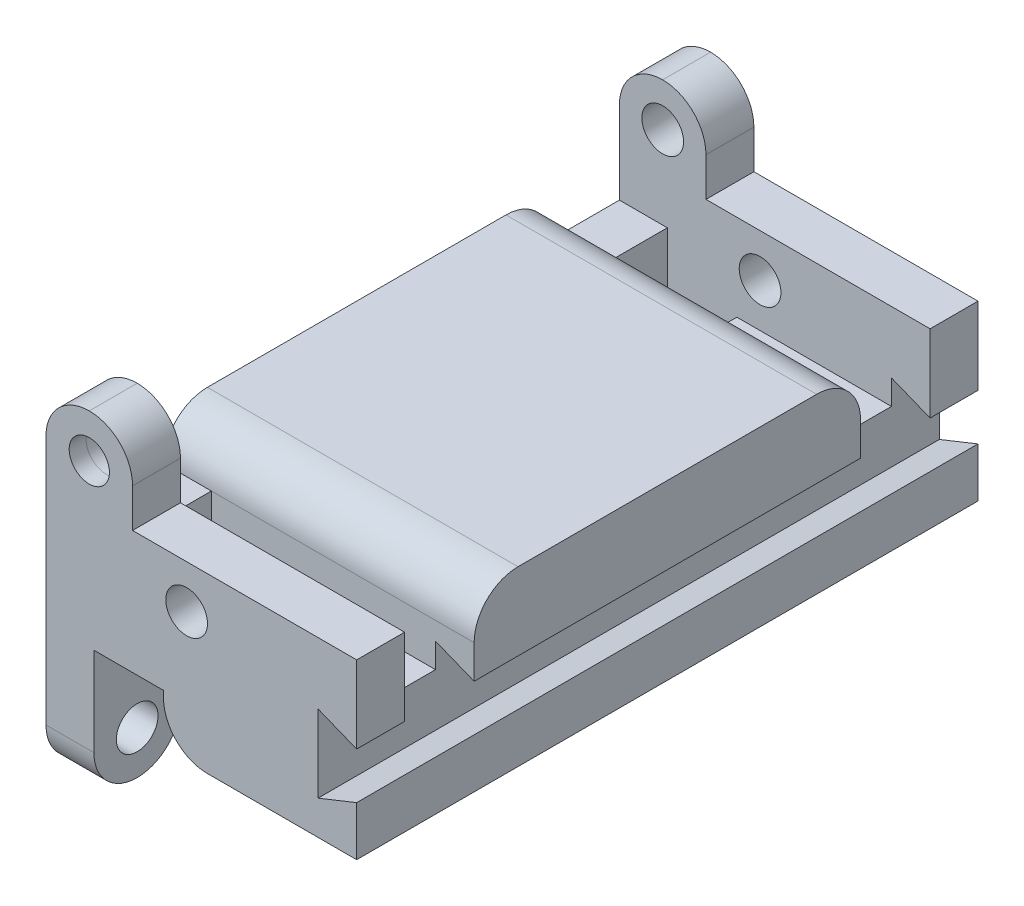
SolidWorks part; units mm, degrees
ref_plane "Plano frontal" through (0, 0, 0) normal (0, 0, 1) x (1, 0, 0)
ref_plane "Plano superior" through (0, 0, 0) normal (0, 1, 0) x (1, 0, 0)
ref_plane "Plano direito" through (0, 0, 0) normal (1, 0, 0) x (0, 0, -1)
sketch "Esboço1" plane through (0, 0, 0) normal (0, 0, 1) x (1, 0, 0)
  line L0 (0, 0) -> (5.6, 0)
  line L1 (0, 0) -> (0, -11.45)
  line L2 (0, -11.45) -> (40.2, -11.45)
  line L3 (40.2, -11.45) -> (40.2, 0)
  line L4 (40.2, 0) -> (34.6, 0)
  line L5 (5.6, 0) -> (5.6, -5.85)
  line L6 (5.6, -5.85) -> (34.6, -5.85)
  line L7 (34.6, -5.85) -> (34.6, 0)
  circle A0 centre (2.8, -3.35) radius 1.35
  circle A1 centre (37.4, -3.35) radius 1.35
  circle A3 centre (31.1, -8.65) radius 1.35
  circle A4 centre (9.1, -8.65) radius 1.35
  dimension "D6" = 2.7
  dimension "D7" = 3.35
  dimension "D8" = 2.7
  dimension "D9" = 2.8
  dimension "D10" = 2.8
  dimension "D11" = 2.7
  dimension "D12" = 2.7
  dimension "D13" = 3.5
  dimension "D14" = 3.5
  dimension "D15" = 2.8
  dimension "D16" = 2.8
  dimension "D17" = 3.35
  dimension "D1" = 5.6
  dimension "D2" = 11.45
  dimension "D3" = 40.2
  dimension "D4" = 5.6
  dimension "D5" = 5.85
extrude "Ressalto-extrusão1" add sketch "Esboço1" along normal blind 2
sketch "Esboço3" plane through (0, -11.45, 0) normal (0, -1, 0) x (1, 0, 0)
  line L1 (0, 0) -> (40.2, 0)
  line L2 (0, 0) -> (0, 2)
  line L3 (0, 2) -> (40.2, 2)
  line L4 (40.2, 0) -> (40.2, 2)
extrude "Ressalto-extrusão2" add sketch "Esboço3" along normal blind 10.08
sketch "Esboço4" plane through (0, 0, 0) normal (0, 0, -1) x (-1, 0, 0)
  line L0 (0, 0) -> (0, -21.53) construction
  line L1 (-40.2, -21.53) -> (-37.1, -21.53)
  line L2 (-40.2, -21.53) -> (-40.2, -8.69)
  line L3 (-40.2, -8.69) -> (-37.1, -8.69)
  line L4 (-37.1, -21.53) -> (-37.1, -8.69)
  line L5 (0, -8.69) -> (-3.1, -8.69)
  line L6 (0, -8.69) -> (0, -21.53)
  line L7 (0, -21.53) -> (-3.1, -21.53)
  line L8 (-3.1, -8.69) -> (-3.1, -21.53)
  line L9 (0, -21.53) -> (-40.2, -21.53) construction
  dimension "D1" = 12.84
  dimension "D2" = 3.1
  dimension "D3" = 3.1
  dimension "D4" = 12.84
extrude "Ressalto-extrusão3" add sketch "Esboço4" along normal blind 34
sketch "Esboço5" plane through (37.1, 0, 0) normal (-1, 0, 0) x (0, 0, 1)
  line L0 (0, -21.53) -> (0, -8.69) construction
  line L2 (-34, -21.53) -> (0, -21.53) construction
  line L4 (-34, -21.53) -> (-34, -8.69) construction
  circle A0 centre (-6, -14.25) radius 1.35
  circle A2 centre (-28, -14.25) radius 1.35
  dimension "D1" = 2.7
  dimension "D2" = 2.7
  dimension "D3" = 6
  dimension "D4" = 7.28
  dimension "D5" = 7.28
  dimension "D6" = 6
extrude "Corte-extrusão1" cut sketch "Esboço5" against normal through all both and the other way through all
sketch "Esboço7" plane through (0, 0, 0) normal (0, 0, -1) x (-1, 0, 0)
  line L0 (0, 0) -> (0, -8.69) construction
  line L1 (-37.1, -21.53) -> (0, -21.53)
  line L2 (-37.1, -21.53) -> (-37.1, -18.29)
  line L3 (-37.1, -18.29) -> (0, -18.29)
  line L4 (0, -21.53) -> (0, -18.29)
  dimension "D1" = 3.24
extrude "Corte-extrusão2" cut sketch "Esboço7" against normal blind 2
sketch "Esboço12" plane through (0, 0, -34) normal (0, 0, -1) x (-1, 0, 0)
  line L0 (-5.6, 0) -> (0, 0)
  line L1 (-40.2, 0) -> (-34.6, 0)
  line L2 (-40.2, 0) -> (-40.2, -18.29)
  line L3 (-40.2, -18.29) -> (0, -18.29)
  line L4 (0, 0) -> (0, -18.29)
  line L6 (-34.6, 0) -> (-34.6, -5.85)
  line L7 (-34.6, -5.85) -> (-5.6, -5.85)
  line L8 (-5.6, 0) -> (-5.6, -5.85)
  circle A1 centre (-31.1, -8.65) radius 1.35
  circle A2 centre (-9.1, -8.65) radius 1.35
  circle A3 centre (-2.8, -3.35) radius 1.35
  circle A4 centre (-37.4, -3.35) radius 1.35
extrude "Ressalto-extrusão5" add sketch "Esboço12" along normal blind 2
sketch "Esboço18" plane through (0, 0, 0) normal (0, 0, 1) x (1, 0, 0)
  line L0 (3.1, -18.29) -> (3.1, -21.53) construction
  line L1 (0, -18.29) -> (3.1, -18.29)
  line L2 (0, -18.29) -> (0, -21.53)
  line L3 (0, -21.53) -> (3.1, -21.53)
  line L4 (3.1, -18.29) -> (3.1, -21.53)
extrude "Ressalto-extrusão6" add sketch "Esboço18" along normal blind 2
sketch "Esboço19" plane through (0, 0, -34) normal (0, 0, -1) x (-1, 0, 0)
  line L0 (0, -21.53) -> (0, -18.29) construction
  line L1 (-3.1, -21.53) -> (0, -21.53)
  line L2 (-3.1, -21.53) -> (-3.1, -18.29)
  line L3 (-3.1, -18.29) -> (0, -18.29)
  line L4 (0, -21.53) -> (0, -18.29)
  line L6 (-40.2, -21.53) -> (-37.1, -21.53)
  line L7 (-40.2, -21.53) -> (-40.2, -18.29)
  line L8 (-40.2, -18.29) -> (-37.1, -18.29)
  line L9 (-37.1, -21.53) -> (-37.1, -18.29)
extrude "Ressalto-extrusão7" add sketch "Esboço19" along normal blind 2
sketch "Esboço21" plane through (0, 0, 2) normal (0, 0, 1) x (1, 0, 0)
  line L0 (37.1, -21.53) -> (40.2, -21.53)
  line L1 (0, 0) -> (5.6, 0)
  line L2 (0, 0) -> (0, -21.53)
  line L3 (0, -21.53) -> (3.1, -21.53)
  line L4 (40.2, 0) -> (40.2, -21.53)
  line L6 (5.6, 0) -> (5.6, -5.85)
  line L7 (5.6, -5.85) -> (34.6, -5.85)
  line L8 (34.6, 0) -> (34.6, -5.85)
  line L9 (3.1, -18.29) -> (37.1, -18.29)
  line L10 (3.1, -18.29) -> (3.1, -21.53)
  line L12 (37.1, -18.29) -> (37.1, -21.53)
  line L13 (34.6, 0) -> (40.2, 0)
  circle A0 centre (2.8, -3.35) radius 1.3018
  circle A1 centre (9.1, -8.65) radius 1.35
  circle A2 centre (31.1, -8.65) radius 1.35
  circle A3 centre (37.4, -3.35) radius 1.35
extrude "Ressalto-extrusão8" add sketch "Esboço21" along normal blind 1.1
sketch "Esboço22" plane through (0, 0, -36) normal (0, 0, -1) x (-1, 0, 0)
  line L0 (-5.6, 0) -> (0, 0)
  line L1 (-40.2, 0) -> (-34.6, 0)
  line L2 (-40.2, 0) -> (-40.2, -21.53)
  line L3 (-40.2, -21.53) -> (-37.1, -21.53)
  line L4 (0, 0) -> (0, -21.53)
  line L6 (-37.1, -21.53) -> (-37.1, -18.29)
  line L7 (-37.1, -18.29) -> (-3.1, -18.29)
  line L8 (-3.1, -21.53) -> (-3.1, -18.29)
  line L9 (-34.6, -5.85) -> (-5.6, -5.85)
  line L10 (-34.6, -5.85) -> (-34.6, 0)
  line L12 (-5.6, -5.85) -> (-5.6, 0)
  line L13 (-3.1, -21.53) -> (0, -21.53)
  circle A0 centre (-37.4, -3.35) radius 1.35
  circle A1 centre (-31.1, -8.65) radius 1.35
  circle A2 centre (-9.1, -8.65) radius 1.35
  circle A3 centre (-2.8, -3.35) radius 1.35
extrude "Ressalto-extrusão9" add sketch "Esboço22" along normal blind 1.1
sketch "Esboço23" plane through (0, -21.53, 0) normal (0, -1, 0) x (1, 0, 0)
  line L0 (3.1, -37.1) -> (3.1, 3.1) construction
  line L1 (0, 3.1) -> (3.1, 3.1)
  line L2 (0, 3.1) -> (0, -2.5)
  line L3 (0, -2.5) -> (3.1, -2.5)
  line L4 (3.1, 3.1) -> (3.1, -2.5)
  line L5 (40.2, -37.1) -> (40.2, 3.1) construction
  line L6 (0, -37.1) -> (3.1, -37.1)
  line L7 (0, -37.1) -> (0, -31.5)
  line L8 (0, -31.5) -> (3.1, -31.5)
  line L9 (3.1, -37.1) -> (3.1, -31.5)
  line L10 (37.1, -37.1) -> (40.2, -37.1)
  line L11 (37.1, -37.1) -> (37.1, -31.5)
  line L12 (37.1, -31.5) -> (40.2, -31.5)
  line L13 (40.2, -37.1) -> (40.2, -31.5)
  line L15 (37.1, 3.1) -> (40.2, 3.1)
  line L16 (37.1, 3.1) -> (37.1, -2.5)
  line L17 (37.1, -2.5) -> (40.2, -2.5)
  line L18 (40.2, 3.1) -> (40.2, -2.5)
  dimension "D1" = 5.6
  dimension "D2" = 5.6
  dimension "D3" = 5.6
  dimension "D4" = 5.6
extrude "Ressalto-extrusão10" add sketch "Esboço23" along normal blind 5.85
sketch "Esboço24" plane through (0, 0, 0) normal (-1, 0, 0) x (0, 0, 1)
  line L1 (-31.5, -27.38) -> (-31.5, -21.53) construction
  line L2 (3.1, 0) -> (3.1, -27.38) construction
  line L3 (3.1, -27.38) -> (-2.5, -27.38) construction
  line L4 (-31.5, -27.38) -> (-37.1, -27.38) construction
  circle A0 centre (-34.3, -19.55) radius 1.35
  circle A1 centre (0.3, -19.55) radius 1.35
  point P10 (0.3, -27.38)
  dimension "D1" = 2.7
  dimension "D2" = 2.7
  dimension "D3" = 2.8
  dimension "D4" = 2.8
  dimension "D5" = 7.83
  dimension "D6" = 7.83
extrude "Corte-extrusão3" cut sketch "Esboço24" against normal up to surface (40.2 mm away) up to face at (40.2, -14.25, -4.65)
sketch "Esboço25" plane through (0, -18.29, 0) normal (0, -1, 0) x (1, 0, 0)
  line L6 (3.1, -37.1) -> (7.6, -37.1)
  line L7 (3.1, -37.1) -> (3.1, -34)
  line L8 (3.1, -34) -> (7.6, -34)
  line L9 (37.1, -37.1) -> (37.1, -34)
  line L10 (32.6, 3.1) -> (37.1, 3.1)
  line L11 (3.1, 3.1) -> (7.6, 3.1)
  line L16 (3.1, 3.1) -> (3.1, 0)
  line L17 (3.1, 0) -> (7.6, 0)
  line L18 (37.1, 3.1) -> (37.1, 0)
  line L22 (7.6, 3.1) -> (7.6, 0)
  line L25 (37.1, 0) -> (32.6, 0)
  line L26 (32.6, 3.1) -> (32.6, 0)
  line L28 (32.6, -34) -> (37.1, -34)
  line L32 (7.6, -34) -> (7.6, -37.1)
  line L33 (37.1, -37.1) -> (32.6, -37.1)
  line L36 (32.6, -37.1) -> (32.6, -34)
  dimension "D1" = 4.5
  dimension "D2" = 4.5
  dimension "D3" = 4.5
  dimension "D4" = 4.5
sketch "Esboço27" plane through (0, -21.53, 0) normal (0, -1, 0) x (1, 0, 0)
  line L28 (0, -2.5) -> (3.1, -2.5)
  line L29 (0, -2.5) -> (0, -31.5)
  line L30 (0, -31.5) -> (3.1, -31.5)
  line L31 (3.1, -2.5) -> (3.1, -31.5)
  line L32 (40.2, -2.5) -> (37.1, -2.5)
  line L33 (40.2, -2.5) -> (40.2, -31.5)
  line L34 (40.2, -31.5) -> (37.1, -31.5)
  line L35 (37.1, -2.5) -> (37.1, -31.5)
extrude "Corte-extrusão6" cut sketch "Esboço25" against normal blind 4.48
extrude "Corte-extrusão7" cut sketch "Esboço27" against normal blind 4.48
sketch "Esboço28" plane through (0, -18.29, 0) normal (0, -1, 0) x (1, 0, 0)
  line L1 (7.6, 3.1) -> (32.6, 3.1)
  line L2 (7.6, 3.1) -> (7.6, -37.1)
  line L3 (7.6, -37.1) -> (32.6, -37.1)
  line L4 (32.6, 3.1) -> (32.6, -37.1)
extrude "Corte-extrusão8" cut sketch "Esboço28" against normal blind 1.24
sketch "Esboço29" plane through (0, 0, -34) normal (0, 0, 1) x (1, 0, 0)
  line L1 (7.6, -17.05) -> (32.6, -17.05)
  line L2 (7.6, -17.05) -> (7.6, -11.45)
  line L3 (7.6, -11.45) -> (32.6, -11.45)
  line L4 (32.6, -17.05) -> (32.6, -11.45)
  dimension "D1" = 25
  dimension "D2" = 5.6
extrude "Ressalto-extrusão11" add sketch "Esboço29" along normal up to surface (34 mm away) up to face at (32.45, -8.65, 0)
sketch "Esboço31" plane through (0, -8.69, 0) normal (0, 1, 0) x (1, 0, 0)
  line L40 (0, 34) -> (0, 0) construction
  line L49 (0, 29.5) -> (3.1, 29.5)
  line L50 (0, 29.5) -> (0, 4.5)
  line L51 (0, 4.5) -> (3.1, 4.5)
  line L52 (3.1, 29.5) -> (3.1, 4.5)
  line L53 (3.1, 34) -> (3.1, 0) construction
  line L54 (37.1, 34) -> (37.1, 0) construction
  line L55 (37.1, 29.5) -> (40.2, 29.5)
  line L56 (37.1, 29.5) -> (37.1, 4.5)
  line L57 (37.1, 4.5) -> (40.2, 4.5)
  line L58 (40.2, 29.5) -> (40.2, 4.5)
  line L59 (40.2, 34) -> (40.2, 0) construction
  line L60 (0, 34) -> (3.1, 34) construction
  line L62 (40.2, 0) -> (34.6, 0) construction
  line L63 (34.6, 34) -> (40.2, 34) construction
  dimension "D1" = 25
  dimension "D2" = 4.5
  dimension "D3" = 4.5
  dimension "D4" = 4.5
extrude "Ressalto-extrusão12" add sketch "Esboço31" along normal blind 2.84
sketch "Esboço32" plane through (37.1, 0, 0) normal (-1, 0, 0) x (0, 0, 1)
  line L1 (-29.5, -5.85) -> (-4.5, -5.85)
  line L2 (-29.5, -5.85) -> (-29.5, -11.45)
  line L3 (-29.5, -11.45) -> (-4.5, -11.45)
  line L4 (-4.5, -5.85) -> (-4.5, -11.45)
  dimension "D1" = 25
  dimension "D2" = 5.6
extrude "Ressalto-extrusão13" add sketch "Esboço32" along normal up to surface (34 mm away) up to face at (3.1, -15.3325, -17)
fillet "Filete1" radius 2.84 4 edges at (32.6, -17.05, -17) (7.6, -17.05, -17) (20.1, -5.85, -29.5) (20.1, -5.85, -4.5)
sketch "Esboço33" plane through (0, 0, 0) normal (0, 1, 0) x (1, 0, 0)
  line L1 (0, 37.1) -> (5.6, 37.1)
  line L2 (0, 37.1) -> (0, 34)
  line L3 (0, 34) -> (5.6, 34)
  line L4 (5.6, 37.1) -> (5.6, 34)
  line L5 (34.6, 34) -> (40.2, 34)
  line L6 (34.6, 34) -> (34.6, 37.1)
  line L7 (34.6, 37.1) -> (40.2, 37.1)
  line L8 (40.2, 34) -> (40.2, 37.1)
  line L9 (40.2, -3.1) -> (34.6, -3.1)
  line L10 (40.2, -3.1) -> (40.2, 0)
  line L11 (40.2, 0) -> (34.6, 0)
  line L12 (34.6, -3.1) -> (34.6, 0)
  line L13 (5.6, -3.1) -> (0, -3.1)
  line L14 (5.6, -3.1) -> (5.6, 0)
  line L15 (5.6, 0) -> (0, 0)
  line L16 (0, -3.1) -> (0, 0)
extrude "Corte-extrusão9" cut sketch "Esboço33" against normal blind 0.55
sketch "Esboço35" plane through (0, -27.38, 0) normal (0, -1, 0) x (1, 0, 0)
  line L1 (0, -2.5) -> (3.1, -2.5)
  line L2 (0, -2.5) -> (0, 3.1)
  line L3 (0, 3.1) -> (3.1, 3.1)
  line L4 (3.1, -2.5) -> (3.1, 3.1)
  line L5 (37.1, -2.5) -> (40.2, -2.5)
  line L6 (37.1, -2.5) -> (37.1, 3.1)
  line L7 (37.1, 3.1) -> (40.2, 3.1)
  line L8 (40.2, -2.5) -> (40.2, 3.1)
  line L9 (40.2, -37.1) -> (37.1, -37.1)
  line L10 (40.2, -37.1) -> (40.2, -31.5)
  line L11 (40.2, -31.5) -> (37.1, -31.5)
  line L12 (37.1, -37.1) -> (37.1, -31.5)
  line L13 (3.1, -37.1) -> (0, -37.1)
  line L14 (3.1, -37.1) -> (3.1, -31.5)
  line L15 (3.1, -31.5) -> (0, -31.5)
  line L16 (0, -37.1) -> (0, -31.5)
extrude "Corte-extrusão10" cut sketch "Esboço35" against normal blind 5.03
fillet "Filete2" radius 2.8 16 edges at (34.6, -0.55, 1.55) (40.2, -0.55, 1.55) (0, -0.55, 1.55) (5.6, -0.55, 1.55) (40.2, -0.55, -35.55) (34.6, -0.55, -35.55) (5.6, -0.55, -35.55) (0, -0.55, -35.55) (1.55, -22.35, -31.5) (1.55, -22.35, -37.1) (38.65, -22.35, -37.1) (38.65, -22.35, -31.5) (38.65, -22.35, 3.1) (38.65, -22.35, -2.5) (1.55, -22.35, -2.5) (1.55, -22.35, 3.1)
sketch "Esboço36" plane through (0, 0, 3.1) normal (0, 0, 1) x (1, 0, 0)
  line L0 (17.6, -9.85) -> (17.6, -14.85)
  line L1 (0, -3.35) -> (0, -19.55) construction
  line L5 (20.1, -0.55) -> (20.1, -10.85)
  line L6 (20.1, -13.85) -> (20.1, -22.35)
  line L11 (17.6, -9.85) -> (20.1, -10.85)
  line L13 (17.6, -14.85) -> (20.1, -13.85)
  dimension "D1" = 21.8
  dimension "D2" = 68.199
  dimension "D3" = 68.199
  dimension "D4" = 8.5
  dimension "D5" = 10.3
  dimension "D9" = 2.5
  dimension "D10" = 20.1
  dimension "D11" = 20.1
split "Dividir1" trim tools "Esboço36" bodies to split 139 resulting bodies 140 141
delete or keep bodies "Corpo-Excluir/Manter 1" type delete bodies bodies 141
